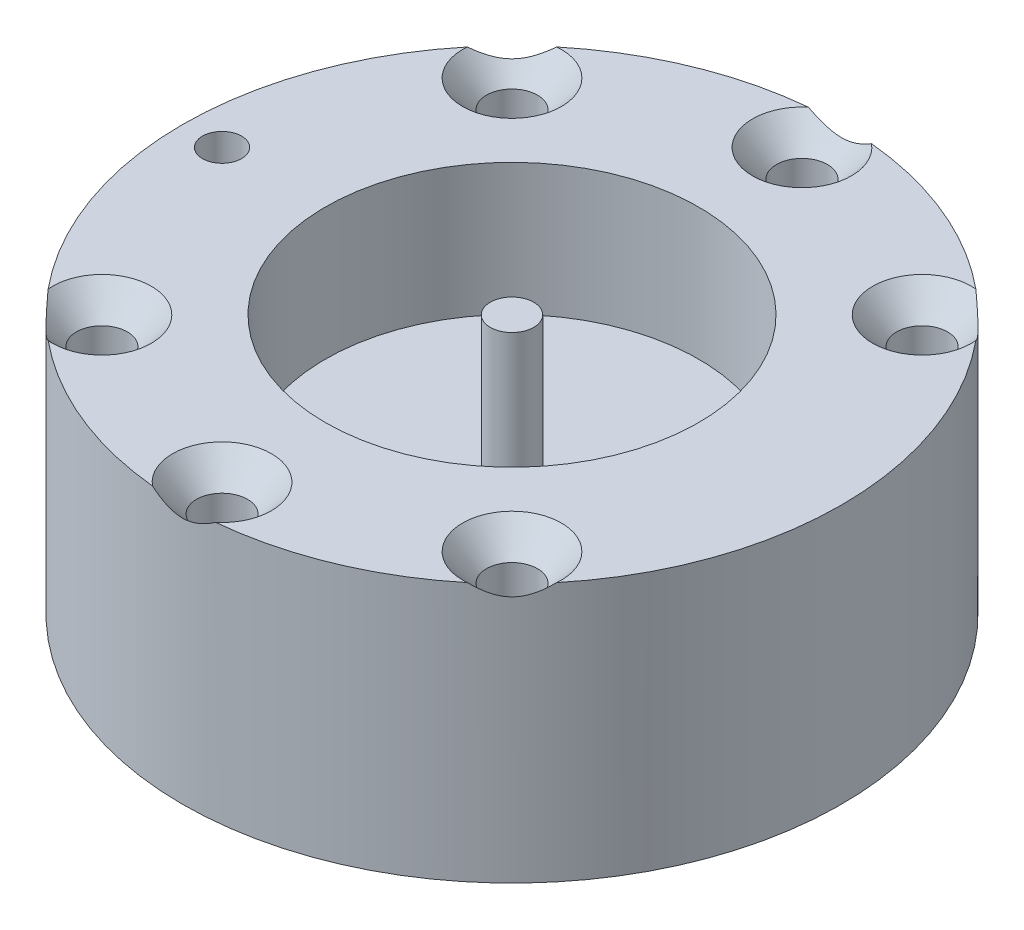
SolidWorks part; units mm, degrees
note: '?' marks a value the reader was unsure of.
other "Top" parameters "D1"=67.5318, "D3"=3.5583, "D4"=2.1466, "D2"=9.3726
material "Copper"
ref_plane "Front Plane" through (0, 0, 0) normal (0, 0, 1) x (1, 0, 0)
ref_plane "Top Plane" through (0, 0, 0) normal (0, 1, 0) x (1, 0, 0)
ref_plane "Right Plane" through (0, 0, 0) normal (1, 0, 0) x (0, 0, -1)
ref_axis "Y Axis" through (0, 15.7353, 0) along (0, -1, 0)?
sketch "outer" plane through (0, 0, 0) normal (0, 1, 0) x (1, 0, 0)
  circle A0 centre (0, 0) radius 19.05
  dimension "D1" = 38.1
extrude "Body" add sketch "outer" along normal blind 14.986
sketch "inner" plane through (0, 0, 0) normal (0, 1, 0) x (1, 0, 0)
  circle A0 centre (0, 0) radius 12.573
  dimension "D1" = 25.146
extrude "Pocket" cut sketch "inner" along normal blind 4.826
sketch "Screw Position" plane through (0, 0, 0) normal (0, 1, 0) x (1, 0, 0)
  point P0 (-11.8539, 11.8539)
  dimension "D1" = 16.764
hole_wizard "CSK for #4 Flat Head Machine Screw1" positions "Sketch7" profile "Sketch8" countersink size "#4" standard "ANSI Inch" end condition through all
sketch "Sketch7" plane through (0, 14.986, 0) normal (0, 1, 0) x (1, 0, 0)
  point P0 (-11.8539, 11.8539)
sketch "Sketch8" plane through (-11.8539, 14.986, -11.8539) normal (1, 0, 0) x (0, 0, 1)
  line L0 (0, 0) -> (0, 14.986)
  line L1 (0, 14.986) -> (1.4732, 14.986)
  line L2 (1.4732, 14.986) -> (1.4732, 1.5925)
  line L3 (1.4732, 1.5925) -> (2.8575, 0)
  line L5 (2.8575, 0) -> (0, 0)
  line L6 (-1.4732, 1.5925) -> (-2.8575, 0) construction
  line L11 (0, -6.35) -> (0, 107.95) construction
  dimension "Thru Hole Dia." = 2.9464
  dimension "Thru Hole Depth" = 14.986
  dimension "Near C'Sink Dia." = 5.715
  dimension "Near C'Sink Angle" = 82
pattern_circular "Screw Holes" count 4 over 360 about axis through (0, 0, 0) along (0, 1, 0) of "CSK for #4 Flat Head Machine Screw1"
sketch "Post Sketch" plane through (0, 0, 0) normal (0, 1, 0) x (1, 0, 0)
  circle A0 centre (0, -5.715) radius 1.0033
  circle A1 centre (5.2984, -5.2984) radius 1.0033
  point P0 (0, -5.715)
  point P1 (5.2984, -5.2984)
  dimension "D3" = 2.0066
  dimension "D4" = 2.0066
  dimension "D1" = 5.715
  dimension "D2" = 7.493
extrude "Post" add sketch "Post Sketch" against normal blind 4.826 from surface at 4.826 starting at face at (0, 4.826, 12.573)
pattern_circular "Posts" count 4 over 360 about axis through (0, 0, 0) along (0, 1, 0) of "Post"
sketch "Flat Cut Sketch" plane through (0, 0, 0) normal (0, 1, 0) x (1, 0, 0)
  line L0 (0, 19.05) -> (0, -19.05) construction
  line L1 (-17.78, 19.05) -> (-20.32, -19.05) construction
  line L2 (17.78, -19.05) -> (20.32, -19.05)
  line L3 (17.78, -19.05) -> (17.78, 19.05)
  line L4 (17.78, 19.05) -> (20.32, 19.05)
  line L5 (20.32, -19.05) -> (20.32, 19.05)
  line L6 (17.78, -19.05) -> (20.32, 19.05) construction
  line L7 (17.78, 19.05) -> (20.32, -19.05) construction
  line L8 (-17.78, -19.05) -> (-20.32, 19.05) construction
  line L9 (-20.32, -19.05) -> (-20.32, 19.05)
  line L10 (-17.78, 19.05) -> (-20.32, 19.05)
  line L11 (-17.78, -19.05) -> (-17.78, 19.05)
  line L12 (-17.78, -19.05) -> (-20.32, -19.05)
  circle A0 centre (0, 0) radius 19.05 construction
  point P5 (19.05, 0)
  point P14 (-19.05, 0)
  dimension "D2" = 2.54
extrude "Flat Cut" [suppressed] cut sketch "Flat Cut Sketch" along normal through all
sketch "Solonoid Sketch" plane through (0, 0, 0) normal (0, 1, 0) x (1, 0, 0)
  circle A0 centre (0, 0) radius 1.2573
  circle A1 centre (0, 0) radius 10.795
  dimension "D1" = 2.5146
  dimension "D2" = 21.59
extrude "Cut-Extrude1" cut sketch "Solonoid Sketch" against normal blind 7.62 from surface at 14.986 starting at face at (0, 14.986, 0)
sketch "Holding Hole Positions" plane through (0, 0, 0) normal (0, 1, 0) x (1, 0, 0)
  point P0 (0, 16.764)
  point P1 (0, -16.764)
  dimension "D1" = 16.764
  dimension "D2" = 16.764
pattern_sketch "Sketch-Pattern1" of "CSK for #4 Flat Head Machine Screw1" driven by "Holding Hole Positions"
sketch "Sketch10" plane through (0, 0, 0) normal (0, 1, 0) x (1, 0, 0)
  point P0 (-16.764, 0)
  dimension "D1" = 16.764
hole_wizard "#4-40 Tapped Hole1" positions "Sketch11" profile "Sketch12" tap size "#4-40" standard "ANSI Inch" end condition through all
sketch "Sketch11" plane through (0, 14.986, 0) normal (0, 1, 0) x (1, 0, 0)
  point P0 (-16.764, 0)
sketch "Sketch12" plane through (-16.764, 14.986, 0) normal (1, 0, 0) x (0, 0, 1)
  line L0 (0, 0) -> (0, 14.986)
  line L1 (0, 14.986) -> (1.1303, 14.986)
  line L2 (1.1303, 14.986) -> (1.1303, 0)
  line L5 (1.1303, 0) -> (0, 0)
  line L11 (0, -6.35) -> (0, 107.95) construction
  dimension "Thru Tap Drill Dia." = 2.2606
  dimension "Thru Tap Drill Depth" = 14.986
cosmetic thread "Hole Thread1" parameters "D2"=2.8448
equation "\"outer_d\"= 3 / 2in"
equation "\"top_h\"= 0.55in"
equation "\"screw_r\"= 0.66in"
equation "\"inner_d\"= 0.99in"
equation "\"inner_h\"= 150mil"
equation "\"D1@outer\" = \"outer_d\""
equation "\"D1@Body\"=\"top_h\" + \"inset_h\""
equation "\"D1@inner\"=\"inner_d\""
equation "\"D1@Pocket\"=\"inner_h\" + \"inset_h\""
equation "\"D1@Screw Position\"=\"screw_r\""
equation "\"post_r1\"= 0.225in"
equation "\"post_r2\"= 0.295in"
equation "\"post_bottom_h\"= 0.04in"
equation "\"D1@Post Sketch\" = \"post_r1\""
equation "\"D2@Post Sketch\" = \"post_r2\""
equation "\"post_d\"= 0.079in"
equation "\"D3@Post Sketch\"=\"post_d\""
equation "\"D4@Post Sketch\"=\"post_d\""
equation "\"D1@Post\" = \"inner_h\" + \"post_bottom_h\""
equation "\"inset_h\"= 0.04in"
equation "\"D1@Flat Cut Sketch\" = \"outer_d\""
equation "\"flat_cut\"= 0.05in"
equation "\"D2@Flat Cut Sketch\" = \"flat_cut\" * 2"
equation "\"solonoid_inner_d\"= 0.099in"
equation "\"solonoid_outer_d\"= 0.850in"
equation "\"solonoid_h\"= 0.300in"
equation "\"D1@Solonoid Sketch\" = \"solonoid_inner_d\""
equation "\"D2@Solonoid Sketch\" = \"solonoid_outer_d\""
equation "\"D1@Cut-Extrude1\"=\"solonoid_h\""
equation "\"D1@Holding Hole Positions\" = \"screw_r\""
equation "\"D2@Holding Hole Positions\" = \"screw_r\""
equation "\"D1@Sketch10\"=\"screw_r\""
